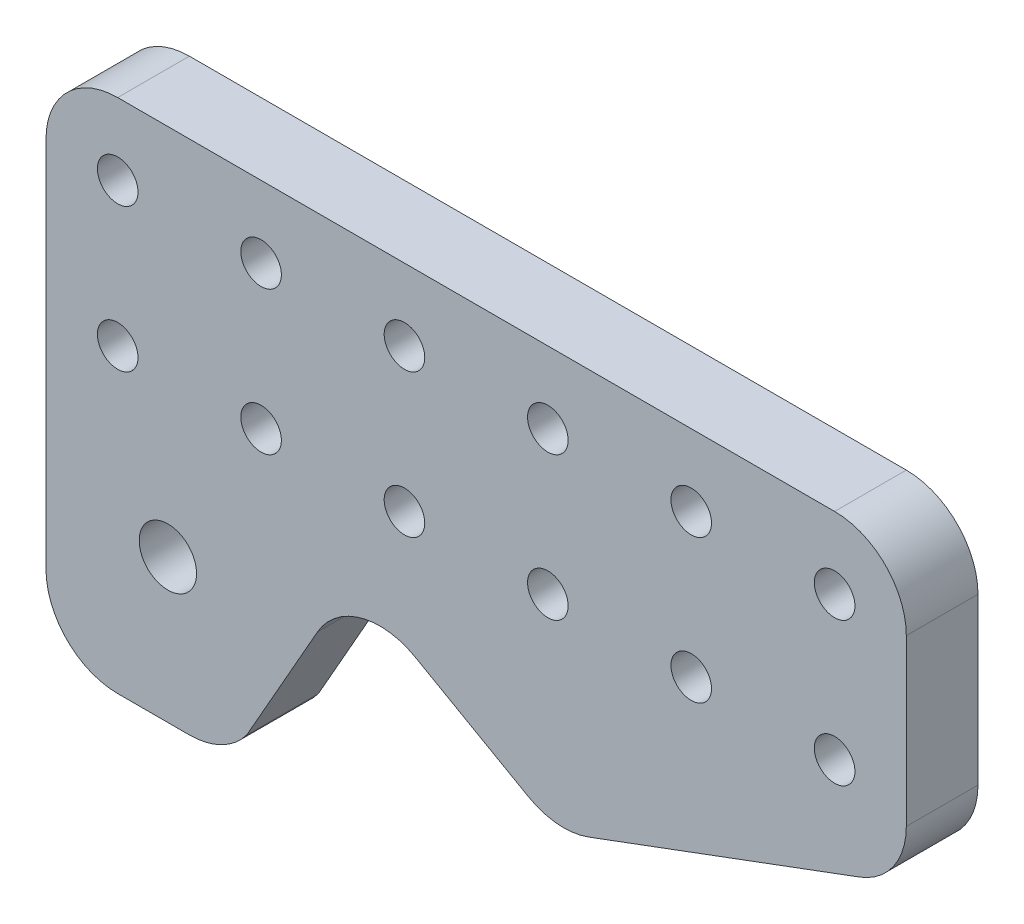
SolidWorks part; units mm, degrees
ref_plane "Front Plane" through (0, 0, 0) normal (0, 0, 1) x (1, 0, 0)
ref_plane "Top Plane" through (0, 0, 0) normal (0, 1, 0) x (1, 0, 0)
ref_plane "Right Plane" through (0, 0, 0) normal (1, 0, 0) x (0, 0, -1)
sketch "Sketch1" plane through (0, 0, 0) normal (0, 0, 1) x (1, 0, 0)
  line L0 (21.59, 0) -> (76.2, 20.32)
  line L3 (0, 45.72) -> (76.2, 45.72)
  line L4 (76.2, 20.32) -> (76.2, 45.72)
  line L7 (0, 0) -> (21.59, 0)
  line L9 (0, 45.72) -> (0, 0)
  circle A0 centre (10.795, 12.7) radius 2.54
  circle A1 centre (69.85, 39.37) radius 1.7977
  circle A2 centre (57.15, 39.37) radius 1.7977
  circle A3 centre (44.45, 39.37) radius 1.7977
  circle A4 centre (31.75, 39.37) radius 1.7977
  circle A5 centre (19.05, 39.37) radius 1.7977
  circle A6 centre (6.35, 39.37) radius 1.7977
  circle A7 centre (57.15, 26.67) radius 1.7977
  circle A8 centre (44.45, 26.67) radius 1.7977
  circle A9 centre (31.75, 26.67) radius 1.7977
  circle A10 centre (19.05, 26.67) radius 1.7977
  circle A11 centre (6.35, 26.67) radius 1.7977
  circle A12 centre (69.85, 26.67) radius 1.7977
  point P8 (10.795, 0)
  dimension "D6" = 5.08
  dimension "D2" = 25.4
  dimension "D3" = 21.59
  dimension "D4" = 76.2
  dimension "D5" = 33.02
  dimension "D7" = 6.35
  dimension "D8" = 6.35
  dimension "D11" = 12.7
  dimension "D9" = 6
  dimension "D10" = 2
extrude "Boss-Extrude1" add sketch "Sketch1" along normal blind 6.35
sketch "Sketch2" plane through (0, 0, 6.35) normal (0, 0, 1) x (1, 0, 0)
  line L0 (17.78, 0) -> (17.78, 2.54)
  line L1 (0, 0) -> (21.59, 0) construction
  line L2 (17.78, 2.54) -> (27.1867, 19.1055)
  line L3 (27.1867, 19.1055) -> (45.2974, 8.8214)
  line L4 (21.59, 0) -> (76.2, 20.32) construction
  line L5 (17.78, 0) -> (21.59, 0)
  line L6 (21.59, 0) -> (45.2974, 8.8214)
  dimension "D1" = 130
  dimension "D2" = 3.81
  dimension "D3" = 2.54
  dimension "D4" = 19.05
extrude "Cut-Extrude1" cut sketch "Sketch2" against normal through all
fillet "Fillet1" radius 6.35 7 edges at (27.1867, 19.1055, 3.175) (45.2974, 8.8214, 3.175) (76.2, 20.32, 3.175) (76.2, 45.72, 3.175) (0, 45.72, 3.175) (0, 0, 3.175) (17.78, 0, 3.175)
